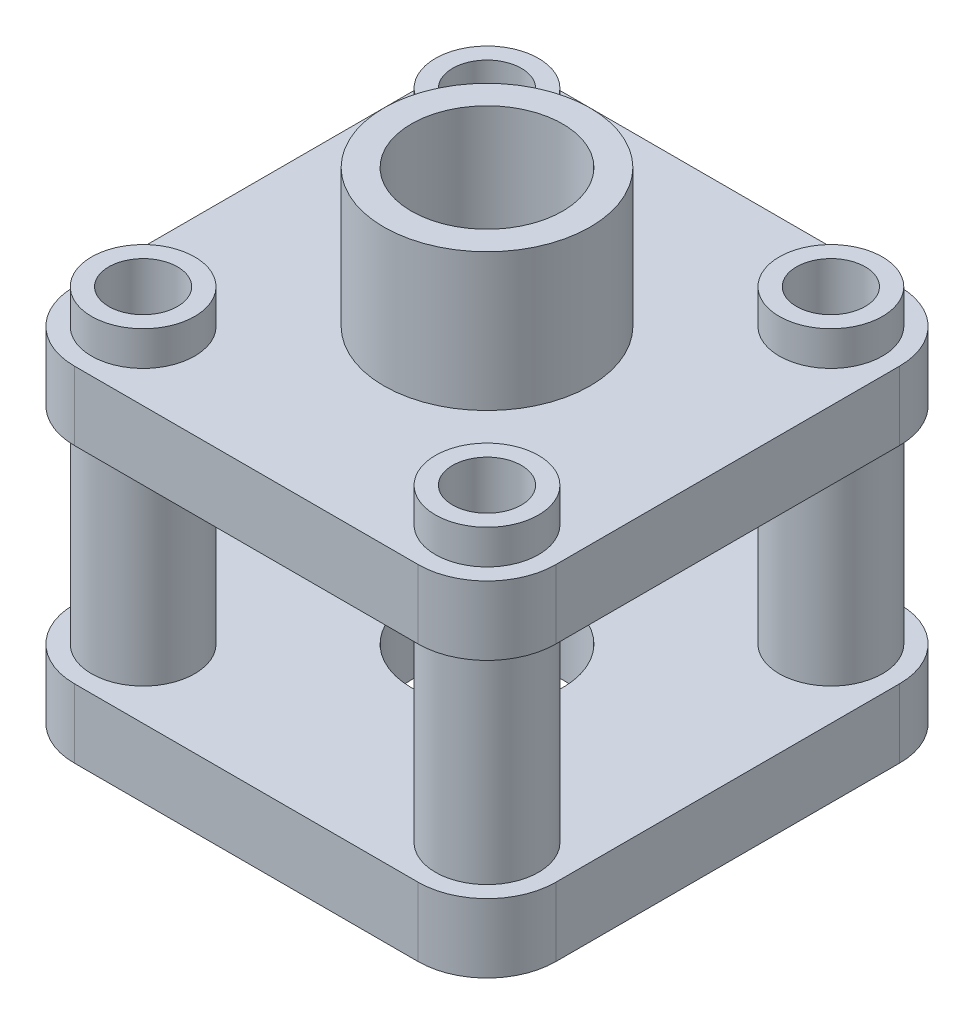
SolidWorks part; units mm, degrees
ref_plane "Front Plane" through (0, 0, 0) normal (0, 0, 1) x (1, 0, 0)
ref_plane "Top Plane" through (0, 0, 0) normal (0, 1, 0) x (1, 0, 0)
ref_plane "Right Plane" through (0, 0, 0) normal (1, 0, 0) x (0, 0, -1)
sketch "Sketch1" plane through (0, 0, 0) normal (0, 1, 0) x (1, 0, 0)
  line L0 (-44.5796, 0) -> (44.5796, 0) construction
  line L1 (-25, 35) -> (25, 35)
  line L2 (-35, 25) -> (-35, -25)
  line L3 (-25, -35) -> (25, -35)
  line L4 (35, 25) -> (35, -25)
  line L5 (-35, 35) -> (35, -35) construction
  line L6 (-35, -35) -> (35, 35) construction
  line L7 (0, 43.8759) -> (0, -43.8759) construction
  circle A0 centre (0, 0) radius 11
  circle A1 centre (0, 0) radius 15
  arc A2 (25, 35) -> (35, 25) centre (25, 25) cw
  arc A3 (25, -35) -> (35, -25) centre (25, -25) ccw
  arc A4 (-35, -25) -> (-25, -35) centre (-25, -25) ccw
  arc A5 (-25, 35) -> (-35, 25) centre (-25, 25) ccw
  circle A6 centre (-25, 25) radius 5
  circle A7 centre (-25, 25) radius 7.5
  circle A8 centre (25, 25) radius 7.5
  circle A9 centre (25, 25) radius 5
  circle A10 centre (25, -25) radius 5
  circle A11 centre (25, -25) radius 7.5
  circle A12 centre (-25, -25) radius 5
  circle A13 centre (-25, -25) radius 7.5
  point P25 (0, 0)
  point P28 (0, 0)
  dimension "D1" = 22
  dimension "D2" = 30
  dimension "D8" = 10
  dimension "D9" = 10
  dimension "D10" = 15
  dimension "D3" = 70
  dimension "D4" = 70
extrude "Boss-Extrude1" add sketch "Sketch1" along normal blind 10 contours A1 A0 | L1 A5 L2 A4 L3 A3 L4 A2 A11 A1 A7 A8 A13 | A13 A12 | A7 A6 | A8 A9 | A11 A10 region at (0, 0, -34.0101) region at (-14.5757, 0, 0) region at (-32.2879, 0, -25) region at (17.7121, 0, -25) region at (17.7121, 0, 25) region at (-32.2879, 0, 25)
extrude "Boss-Extrude2" add sketch "Sketch1<5>" along normal blind 40 contours A7 A6 | A8 A9 | A13 A12 | A11 A10 region at (-32.2879, 0, -25) region at (17.7121, 0, -25) region at (17.7121, 0, 25) region at (-32.2879, 0, 25)
sketch "Sketch1<5>" plane through (0, 0, 0) normal (0, 1, 0) x (1, 0, 0) same geometry as "Sketch1"
sketch "Sketch2" plane through (0, 40, 0) normal (0, 1, 0) x (1, 0, 0)
  line L1 (25, 35) -> (-25, 35) construction
  line L2 (-35, 25) -> (-35, -25) construction
  line L3 (-25, -35) -> (25, -35) construction
  line L4 (35, -25) -> (35, 25) construction
  line L5 (25, 35) -> (-25, 35)
  line L6 (-35, 25) -> (-35, -25)
  line L7 (-25, -35) -> (25, -35)
  line L8 (35, -25) -> (35, 25)
  circle A1 centre (25, 25) radius 7.5 construction
  circle A3 centre (25, -25) radius 7.5 construction
  circle A8 centre (-25, -25) radius 7.5 construction
  circle A10 centre (-25, 25) radius 7.5 construction
  arc A16 (-25, 35) -> (-35, 25) centre (-25, 25) ccw construction
  arc A17 (-35, -25) -> (-25, -35) centre (-25, -25) ccw construction
  arc A18 (25, -35) -> (35, -25) centre (25, -25) ccw construction
  arc A19 (35, 25) -> (25, 35) centre (25, 25) ccw construction
  circle A20 centre (25, 25) radius 7.5
  circle A21 centre (25, -25) radius 7.5
  circle A22 centre (-25, -25) radius 7.5
  circle A23 centre (-25, 25) radius 7.5
  arc A24 (-25, 35) -> (-35, 25) centre (-25, 25) ccw
  arc A25 (-35, -25) -> (-25, -35) centre (-25, -25) ccw
  arc A26 (25, -35) -> (35, -25) centre (25, -25) ccw
  arc A27 (35, 25) -> (25, 35) centre (25, 25) ccw
  circle A30 centre (25, 25) radius 5 construction
  circle A31 centre (25, -25) radius 5 construction
  circle A32 centre (-25, -25) radius 5 construction
  circle A33 centre (-25, 25) radius 5 construction
  circle A34 centre (25, 25) radius 5
  circle A35 centre (25, -25) radius 5
  circle A36 centre (-25, -25) radius 5
  circle A37 centre (-25, 25) radius 5
  circle A38 centre (0, 0) radius 11
  circle A39 centre (0, 0) radius 15
  circle M20 centre (-25, 25) radius 5
  circle M21 centre (-25, 25) radius 7.5
  dimension "D1" = 22
  dimension "D2" = 30
extrude "Boss-Extrude5" add sketch "Sketch2" along normal blind 10 contours L8 A27 L5 A24 L6 A25 L7 A26 A20 A21 A22 M21 region at (31.3711, 40, -31.3711)
extrude "Boss-Extrude6" add sketch "Sketch2<6>" along normal blind 15 contours A22 A36 | M21 M20 | A20 A34 | A21 A35 region at (17.7121, 40, -25) region at (17.7121, 40, 25) region at (-32.2879, 40, 25) region at (-32.2879, 40, -25)
sketch "Sketch2<6>" plane through (0, 40, 0) normal (0, 1, 0) x (1, 0, 0) same geometry as "Sketch2"
extrude "Boss-Extrude7" add sketch "Sketch2<7>" along normal blind 30 contours A39 A38 region at (-14.5757, 40, 0)
sketch "Sketch2<7>" plane through (0, 40, 0) normal (0, 1, 0) x (1, 0, 0) same geometry as "Sketch2"
